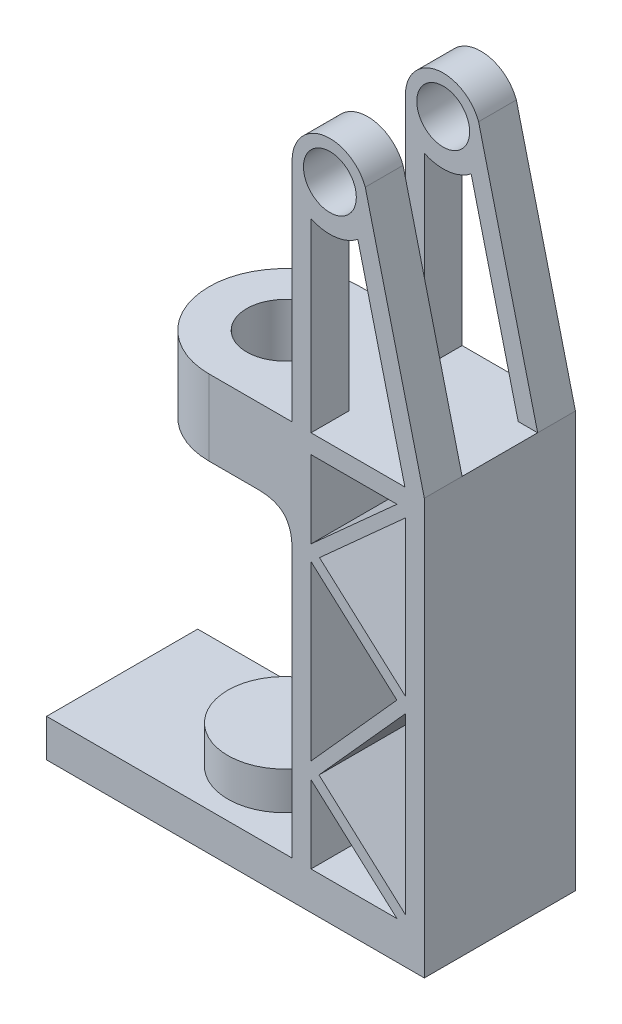
SolidWorks part; units mm, degrees
ref_plane "Front Plane" through (0, 0, 0) normal (0, 0, 1) x (1, 0, 0)
ref_plane "Top Plane" through (0, 0, 0) normal (0, 1, 0) x (1, 0, 0)
ref_plane "Right Plane" through (0, 0, 0) normal (1, 0, 0) x (0, 0, -1)
sketch "Sketch1" plane through (0, 0, 0) normal (0, 0, 1) x (1, 0, 0)
  line L0 (0, 0) -> (0, 60)
  line L6 (19.3666, 63.5025) -> (35, 0)
  line L7 (35, 0) -> (35, -110)
  line L8 (35, -110) -> (0, -110)
  line L9 (0, -90) -> (0, -20)
  line L10 (0, -20) -> (-42, -20)
  line L11 (-42, -20) -> (-42, 0)
  line L12 (-42, 0) -> (0, 0)
  line L13 (0, -90) -> (0, -110)
  arc A0 (19.3666, 63.5025) -> (0, 60) centre (10, 60) ccw
  circle A1 centre (10, 60) radius 7
  dimension "D3" = 180
  dimension "D6" = 10
  dimension "D9" = 14
  dimension "D4" = 42
  dimension "D5" = 19.3666
  dimension "D10" = 35
  dimension "D11" = 60
  dimension "D12" = 20
extrude "Boss-Extrude1" add sketch "Sketch1" along normal blind 20 and the other way blind 20
sketch "Sketch2" plane through (0, 0, 20) normal (0, 0, 1) x (1, 0, 0)
  line L0 (35, -110) -> (35, -100)
  line L1 (35, -110) -> (35, 0) construction
  line L2 (-65, -100) -> (35, -100)
  line L4 (35, -110) -> (-65, -110)
  line L5 (-65, -110) -> (-65, -100)
  dimension "D1" = 100
  dimension "D2" = 10
extrude "Boss-Extrude2" add sketch "Sketch2" against normal blind 40
fillet "Fillet1" radius 20 2 edges at (-42, -10, -20) (-42, -10, 20)
sketch "Sketch3" plane through (0, 0, 0) normal (0, 1, 0) x (1, 0, 0)
  circle A1 centre (-22, 0) radius 10
  arc A2 (-42, 0) -> (-22, -20) centre (-22, 0) ccw construction
  dimension "D1" = 20
extrude "Cut-Extrude1" cut sketch "Sketch3" against normal blind 40
fillet "Fillet2" radius 10 1 edges at (0, -20, 0) curvature continuous yes
sketch "Sketch4" plane through (0, 0, 0) normal (-1, 0, 0) x (0, 0, 1)
  line L0 (-20, 60) -> (-20, 0) construction
  line L1 (-10, 0) -> (10, 0)
  line L2 (-10, 0) -> (-10, 70)
  line L3 (-10, 70) -> (10, 70)
  line L4 (10, 0) -> (10, 70)
  line L5 (20, 60) -> (20, 0) construction
  line L7 (20, 70) -> (-20, 70) construction
  line L8 (-20, 0) -> (20, 0) construction
  dimension "D1" = 10
  dimension "D2" = 10
  dimension "D4" = 0
extrude "Cut-Extrude2" cut sketch "Sketch4" against normal blind 50
sketch "Sketch5" plane through (0, -100, 0) normal (0, 1, 0) x (1, 0, 0)
  line L0 (0, 0) -> (-22, 0) construction
  line L1 (0, -20) -> (0, 20) construction
  circle A0 centre (-22, 0) radius 15
  dimension "D2" = 30
  dimension "D1" = 22
extrude "Boss-Extrude3" add sketch "Sketch5" along normal blind 10
sketch "Sketch6" plane through (0, 0, 20) normal (0, 0, 1) x (1, 0, 0)
  line L1 (0, 0) -> (-22, 0) construction
  line L4 (5, 0) -> (29.8507, 0)
  line L16 (5, -5) -> (-17, -5)
  line L17 (-17, -5) -> (-17, -15)
  line L18 (-17, -15) -> (-10, -15)
  line L19 (5, -30) -> (5, -105)
  line L21 (30, -105) -> (30, -0.6064)
  line L22 (30, -0.6064) -> (14.5932, 61.9755)
  line L23 (5, 60) -> (5, -5)
  line L30 (29.8507, 0) -> (17.4043, 50.5567)
  line L31 (5, 49.0913) -> (5, 0)
  line L35 (5, -105) -> (30, -105)
  line L53 (-65, -110) -> (35, -110) construction
  line L55 (5, -5) -> (5, -100)
  line L56 (5, -100) -> (30, -100)
  line L57 (30, -5) -> (30, -100)
  line L58 (35, -110) -> (35, 0) construction
  line L59 (0, -30) -> (0, -100) construction
  line L68 (5, -5) -> (30, -5)
  line L73 (27.7577, -5) -> (5, -25.482)
  line L74 (5, -29.5156) -> (27.7365, -49.9229)
  line L75 (27.7365, -49.9229) -> (5, -75.2544)
  line L76 (5, -79.518) -> (27.7577, -100)
  line L77 (30, -7.018) -> (7.244, -27.4985)
  line L78 (7.244, -27.4985) -> (30, -47.9234)
  line L79 (30, -51.8923) -> (7.1169, -77.3872)
  line L80 (7.1169, -77.3872) -> (30, -97.982)
  arc A2 (14.5932, 61.9755) -> (5, 60) centre (10, 60) ccw
  circle A5 centre (10, 60) radius 12
  arc A6 (5, 49.0913) -> (17.4043, 50.5567) centre (10, 60) ccw
  spline S2 degree 3 poles (20.0222, 984.5447) (-63.7616, -64.0629) (-32.5371, -12.6542) (-6.438, -15.1586) (-5.9338, -15.226) (-4.9303, -15.4067) (-4.4295, -15.5206) (-2.945, -15.941) (-1.9991, -16.3198) (-0.6606, -17.0689) (-0.2249, -17.3514) (0.5926, -17.9663) (1.3604, -18.6321) (2.0281, -19.4005) (2.4912, -20.0154) (2.6397, -20.2275) (2.9201, -20.6584) (3.0525, -20.8777) (3.4272, -21.5465) (3.6473, -22.0068) (4.0335, -22.954) (4.2002, -23.4437) (4.6191, -24.9236) (4.7919, -25.9253) (7.3504, -52.4998) (-43.9489, -86.3397) (996.8626, 97.2219) knots -3.035275 -3.035275 -3.035275 -3.035275 0.125 0.125 0.1875 0.1875 0.25 0.25 0.375 0.375 0.4375 0.4375 0.5 0.5625 0.5625 0.59375 0.59375 0.625 0.625 0.6875 0.6875 0.75 0.75 0.875 0.875 4.03101 4.03101 4.03101 4.03101 only from (-10, -15) to (5, -30)
  dimension "D3" = 5
  dimension "D4" = 10
  dimension "D5" = 5
  dimension "D6" = 5
  dimension "D1" = 5
  dimension "D2" = 5
extrude "Cut-Extrude4" cut sketch "Sketch6" against normal blind 56 and the other way blind 10 contours L77 L78 L57 | L73 L68 L55 | L75 L74 L55 | L79 L80 L57 | L76 L55 L56 | L30 A6 L31 L4 region at (12.5859, -11.8273, 20) region at (12.5788, -51.5643, 20) region at (22.4147, -27.48, 20) region at (22.3723, -75.7538, 20) region at (12.5859, -93.1727, 20)
